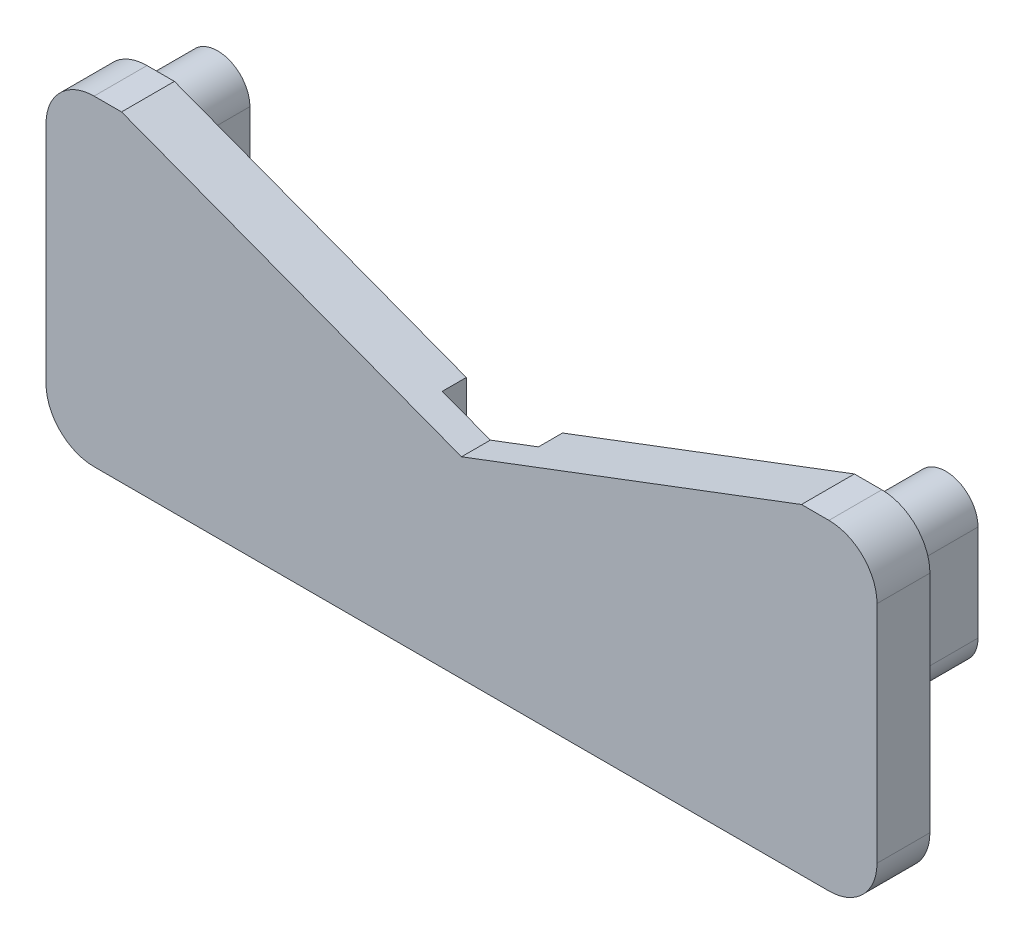
SolidWorks part; units mm, degrees
ref_plane "Front Plane" through (0, 0, 0) normal (0, 0, 1) x (1, 0, 0)
ref_plane "Top Plane" through (0, 0, 0) normal (0, 1, 0) x (1, 0, 0)
ref_plane "Right Plane" through (0, 0, 0) normal (1, 0, 0) x (0, 0, -1)
sketch "Sketch1" plane through (0, 0, 0) normal (0, 0, 1) x (1, 0, 0)
  line L0 (-37.85, 11.3382) -> (-37.85, 1.3382) construction
  line L1 (-38.2, -16.6882) -> (38.2, -16.6882)
  line L2 (-43.2, -11.6882) -> (-43.2, 11.6882)
  line L3 (-38.2, 16.6882) -> (38.2, 16.6882)
  line L4 (43.2, -11.6882) -> (43.2, 11.6882)
  line L5 (-43.2, -16.6882) -> (43.2, 16.6882) construction
  line L6 (-43.2, 16.6882) -> (43.2, -16.6882) construction
  line L7 (-34.5, 11.3382) -> (-34.5, 1.3382)
  line L8 (-41.2, 11.3382) -> (-41.2, 1.3382)
  line L9 (37.85, 11.3382) -> (37.85, 1.3382) construction
  line L10 (41.2, 11.3382) -> (41.2, 1.3382)
  line L11 (34.5, 11.3382) -> (34.5, 1.3382)
  line L12 (-37.85, 6.3382) -> (37.85, 6.3382) construction
  line L13 (-35.3467, 16.6882) -> (0, 3.3118)
  line L14 (0, 3.3118) -> (35.3467, 16.6882)
  line L15 (-5, 5.204) -> (-5, -16.6882)
  line L16 (5, 5.204) -> (5, -16.6882)
  arc A0 (-34.5, 11.3382) -> (-41.2, 11.3382) centre (-37.85, 11.3382) ccw
  arc A1 (-41.2, 1.3382) -> (-34.5, 1.3382) centre (-37.85, 1.3382) ccw
  arc A2 (41.2, 11.3382) -> (34.5, 11.3382) centre (37.85, 11.3382) ccw
  arc A3 (34.5, 1.3382) -> (41.2, 1.3382) centre (37.85, 1.3382) ccw
  arc A4 (-38.2, -16.6882) -> (-43.2, -11.6882) centre (-38.2, -11.6882) cw
  arc A5 (38.2, -16.6882) -> (43.2, -11.6882) centre (38.2, -11.6882) ccw
  arc A6 (38.2, 16.6882) -> (43.2, 11.6882) centre (38.2, 11.6882) cw
  arc A7 (-43.2, 11.6882) -> (-38.2, 16.6882) centre (-38.2, 11.6882) cw
  point P0 (0, 0)
  point P8 (-37.85, 6.3382)
  point P13 (37.85, 6.3382)
  point P22 (0, 6.3382)
  dimension "D5" = 5
  dimension "D1" = 6.7
  dimension "D2" = 69
  dimension "D3" = 2
  dimension "D4" = 5.35
  dimension "D6" = 10
  dimension "D7" = 20
  dimension "D8" = 10
extrude "Boss-Extrude1" add sketch "Sketch1" along normal blind 2.5 contours L8 A1 L7 A0 | L11 A3 L10 A2 | A7 L2 A4 L1 L15 L13 L3 A1 L8 A0 L7 | A6 L3 L14 L16 L1 A5 L4 A3 L11 A2 L10 region at (-24.0662, -2.9249, 0) region at (24.0662, -2.9249, 0) region at (-37.85, 6.3382, 0) region at (37.85, 6.3382, 0)
extrude "Boss-Extrude3" add sketch "Sketch1<4>" along normal blind 3 from surface contours A7 L2 A4 L1 L15 L13 L3 A1 L8 A0 L7 | L16 L14 L13 L15 L1 | A6 L3 L14 L16 L1 A5 L4 A3 L11 A2 L10 | L11 A3 L10 A2 | L8 A1 L7 A0 region at (-24.0662, -2.9249, 0) region at (0, -6.208, 0) region at (24.0662, -2.9249, 0) region at (-37.85, 6.3382, 0) region at (37.85, 6.3382, 0) starting at face at (-30.0311, 0.7434, 2.5)
sketch "Sketch1<4>" plane through (0, 0, 0) normal (0, 0, 1) x (1, 0, 0) same geometry as "Sketch1"
extrude "Boss-Extrude2" add sketch "Sketch1<3>" against normal blind 7 contours L11 A3 L10 A2 | L8 A1 L7 A0 region at (-37.85, 6.3382, 0) region at (37.85, 6.3382, 0)
sketch "Sketch1<3>" plane through (0, 0, 0) normal (0, 0, 1) x (1, 0, 0) same geometry as "Sketch1"
equation "\"D4@Sketch1\"=\"D1@Sketch1\"/2 + \"D3@Sketch1\""
